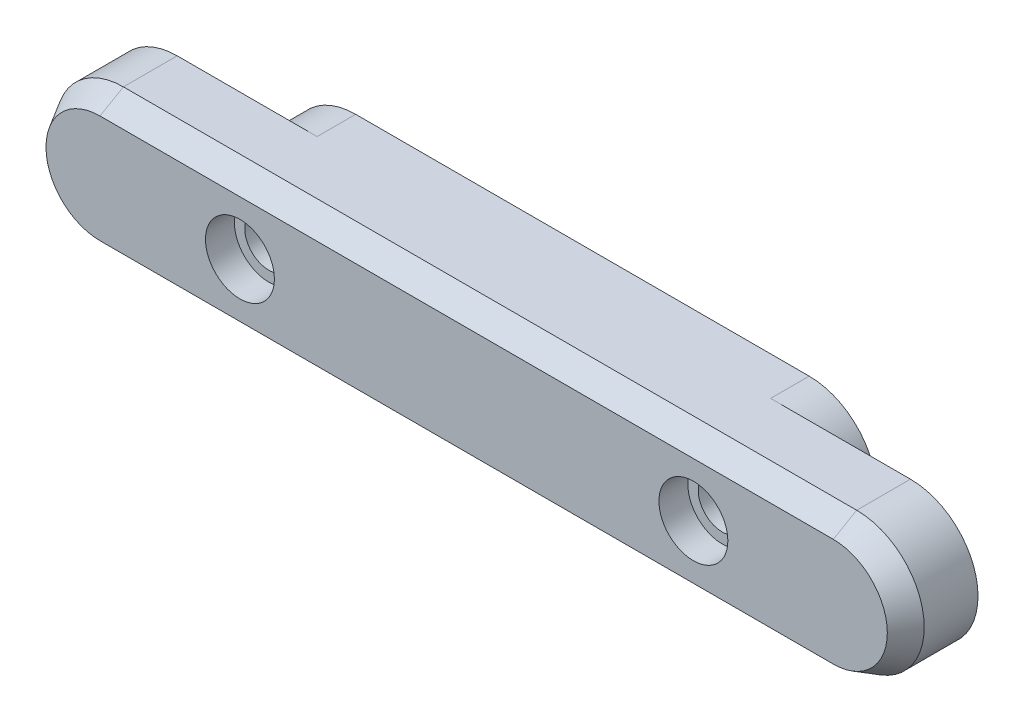
SolidWorks part; units mm, degrees
note: '?' marks a value the reader was unsure of.
ref_plane "Front Plane" through (0, 0, 0) normal (0, 0, 1) x (1, 0, 0)
ref_plane "Top Plane" through (0, 0, 0) normal (0, 1, 0) x (1, 0, 0)
ref_plane "Right Plane" through (0, 0, 0) normal (1, 0, 0) x (0, 0, -1)
sketch "Sketch1" plane through (0, 0, 0) normal (0, 0, 1) x (1, 0, 0)
  line L0 (-22.5, 0) -> (-22.5, 13.8536) construction
  line L1 (-19, -3.5) -> (19, -3.5)
  line L2 (-19, -3.5) -> (-19, 3.5)
  line L3 (-19, 3.5) -> (19, 3.5)
  line L4 (19, -3.5) -> (19, 3.5)
  line L5 (-19, -3.5) -> (19, 3.5) construction
  line L6 (-19, 3.5) -> (19, -3.5) construction
  line L7 (22.5, 0) -> (22.5, 12.6215) construction
  line L8 (11.75, 0) -> (-11.75, 0) construction
  line L10 (-10.5, 0) -> (-10.5, 3.5939) construction
  line L11 (10.5, 0) -> (10.5, 3.7936) construction
  arc A0 (19, 3.5) -> (19, -3.5) centre (19, 0) cw
  arc A1 (-19, 3.5) -> (-19, -3.5) centre (-19, 0) ccw
  circle A2 centre (-11.75, 0) radius 1.25
  circle A3 centre (11.75, 0) radius 1.25
  point P0 (0, 0)
  point P16 (0, 0)
  point P22 (0, 0)
  point P23 (0, 0)
  dimension "D3" = 2.5
  dimension "D4" = 2.5
  dimension "D1" = 7
  dimension "D2" = 45
  dimension "D5" = 21
extrude "Boss-Extrude1" add sketch "Sketch1" along normal blind 4 contours L1 L4 L3 L2 A3 A2 | L2 A1 | A0 L4
chamfer "Chamfer1" distance 0.7 angle 60 4 edges at (0, -3.5, 4) (-22.5, 0, 4) (22.5, 0, 4) (0, 3.5, 4) first distance on face at (13, 0, 4)
sketch "Sketch2" plane through (0, 0, 0) normal (0, 0, -1) x (-1, 0, 0)
  line L0 (11.75, 3.5) -> (-11.75, 3.5)
  line L1 (-11.75, -3.5) -> (11.75, -3.5)
  line L2 (11.75, 1.7859) -> (-11.75, 1.7859) construction
  circle A0 centre (-11.75, 0) radius 3.5
  circle A1 centre (11.75, 0) radius 3.5
  circle A2 centre (-11.75, 0) radius 1.7859
  circle A3 centre (11.75, 0) radius 1.7859
  dimension "D1" = 3.5719
extrude "Boss-Extrude2" add sketch "Sketch2" along normal blind 2
sketch "Sketch3" plane through (0, 0, 0) normal (0, 0, -1) x (-1, 0, 0)
  line L0 (-19, 0) -> (19, 0) construction
  circle A0 centre (-19, 0) radius 1.25
  circle A1 centre (19, 0) radius 1.25
  arc A2 (-19, 3.5) -> (-19, -3.5) centre (-19, 0) ccw construction
  dimension "D1" = 2.5
  dimension "D2" = 2.5
extrude "Cut-Extrude1" cut sketch "Sketch3" against normal blind 3.5
sketch "Sketch4" plane through (0, 0, 4) normal (0, 0, 1) x (1, 0, 0)
  circle A0 centre (-11.75, 0) radius 1.7859
  circle A1 centre (11.75, 0) radius 1.7859
  dimension "D1" = 3.5719
  dimension "D2" = 3.5719
extrude "Cut-Extrude2" cut sketch "Sketch4" against normal blind 1.5
ref_axis "Axis1" through (-11.75, 0, 2.5) along (0, 0, -1)?
ref_axis "Axis2" through (11.75, 0, 2.5) along (0, 0, -1)?
ref_plane "Plane1" through (0, 0, 0) normal (0, 1, 0) x (1, 0, 0)
